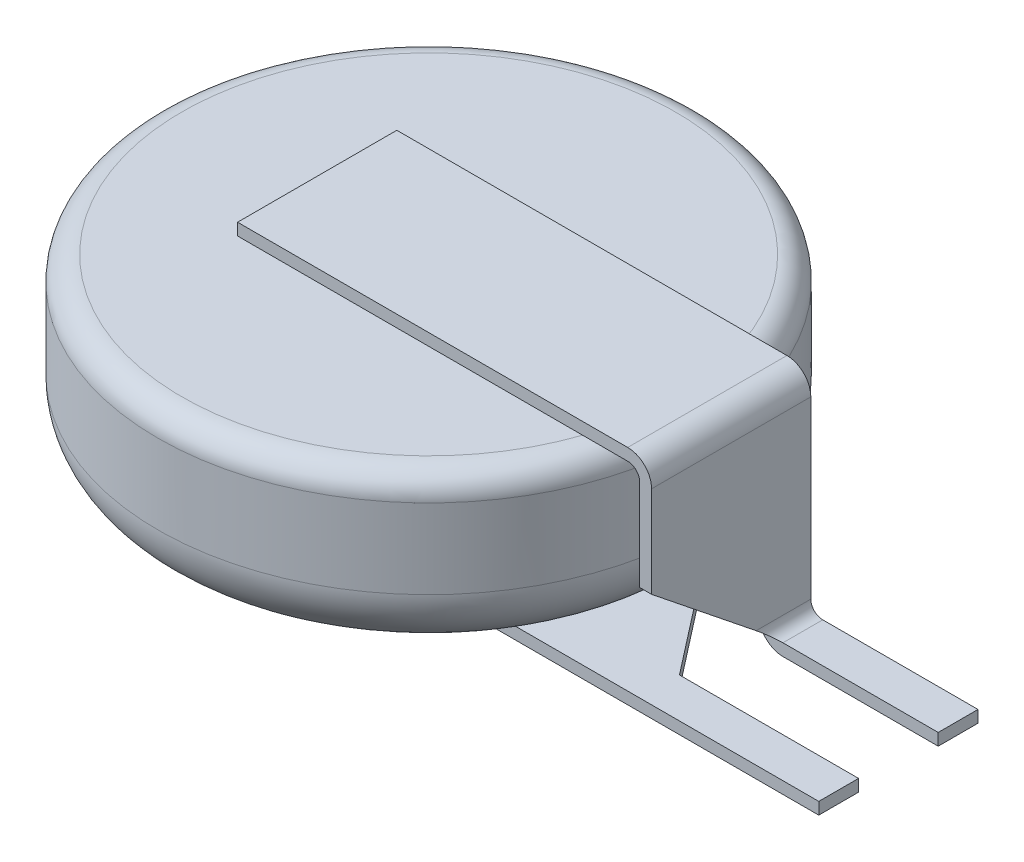
SolidWorks part; units mm, degrees
ref_plane "前视基准面" through (0, 0, 0) normal (0, 0, 1) x (1, 0, 0)
ref_plane "上视基准面" through (0, 0, 0) normal (0, 1, 0) x (1, 0, 0)
ref_plane "右视基准面" through (0, 0, 0) normal (1, 0, 0) x (0, 0, -1)
sketch "草图1" plane through (0, 0, 0) normal (0, 0, 1) x (1, 0, 0)
  line L0 (0, 0) -> (0, 2.8) construction
  line L1 (0.6006, 0.0061) -> (0.6006, 2.6398) construction
  line L2 (0, 2.65) -> (3.4, 2.65)
  line L3 (3.4, 2.65) -> (3.4, 0.552)
  line L4 (3.4, 0.552) -> (2.6, 0.552)
  line L5 (2.6, 0.552) -> (2.5054, 0.4126)
  line L6 (2.5054, 0.4126) -> (2.3701, 0.4126)
  line L7 (2.3701, 0.4126) -> (2.1919, 0.15)
  line L8 (2.1919, 0.15) -> (0, 0.15)
  line L9 (0, 2.65) -> (0, 0.15)
  line L10 (3.1725, 2.65) -> (3.4, 2.35) construction
  dimension "D1" = 2.8
  dimension "D2" = 3.4
  dimension "D3" = 2.5
  dimension "D4" = 0.15
  dimension "D5" = 0.8
  dimension "D6" = 124.16
  dimension "D7" = 0.3
revolve "旋转1" add sketch "草图1" angle 360 about L9
fillet "圆角1" radius 0.3 1 edges at (-3.4, 2.65, 0)
fillet "圆角2" radius 0.8 1 edges at (-3.4, 0.552, 0)
fillet "圆角3" radius 0.2 1 edges at (-2.1919, 0.15, 0)
sketch "草图3" plane through (0, 0, 0) normal (0, 0, 1) x (1, 0, 0)
  line L0 (-2.086, 0.15) -> (2.086, 0.15) construction
  line L1 (-1.7984, 0.15) -> (3.65, 0.15)
  line L2 (-1.7984, 0.15) -> (-1.7984, 0)
  line L3 (-1.7984, 0) -> (5.9, 0)
  line L4 (5.9, 0.15) -> (5.9, 0)
  line L5 (3.1, 2.65) -> (-3.1, 2.65) construction
  line L6 (-1.4, 2.65) -> (3.65, 2.65)
  line L7 (-1.4, 2.65) -> (-1.4, 2.8)
  line L8 (-1.4, 2.8) -> (3.8, 2.8)
  line L12 (3.8, 2.8) -> (3.8, 0.15)
  line L14 (3.65, 2.65) -> (3.65, 0.15)
  line L15 (3.8, 0.15) -> (5.9, 0.15)
  line L16 (3.4, 1.352) -> (3.4, 2.35) construction
  line L17 (3.65, 0.15) -> (3.8, 0.15) construction
  point P13 (-1.7984, 0.075)
  dimension "D1" = 2.5
  dimension "D2" = 2.1
  dimension "D3" = 1.4
  dimension "D4" = 1.8
extrude "凸台-拉伸1" add sketch "草图3" along normal mid plane 2
sketch "草图4" plane through (5.9, 0, 0) normal (1, 0, 0) x (0, 0, -1)
  line L0 (-1, 1.352) -> (0.5, 0.15)
  line L1 (-1, 0.15) -> (-1, 2.8) construction
  line L2 (-1, 0.15) -> (1, 0.15) construction
  line L3 (0.5, 0.15) -> (0.5, 0)
  line L4 (-1, 0) -> (1, 0) construction
  line L5 (0.5, 0) -> (-0.5, 0)
  line L6 (-0.5, 0) -> (-0.5, 0.15)
  line L7 (-0.5, 0.15) -> (-1, 0.15)
  line L8 (-1, 0.15) -> (-1, 1.352)
  line L9 (1, 0) -> (1, 0.15) construction
  line L10 (-1, 0) -> (-1, 0.15) construction
  line L11 (-3.4, 1.352) -> (3.4, 1.352) construction
  point P15 (1, 0.075)
  point P18 (-1, 0.075)
  point P19 (-1, 1.352)
  dimension "D1" = 0.5
  dimension "D2" = 0.5
extrude "切除-拉伸1" cut sketch "草图4" against normal up to surface (2.25 mm away) up to face at (3.65, 1.4, 0)
sketch "草图5" plane through (0, 0, 0) normal (0, -1, 0) x (1, 0, 0)
  line L0 (3.65, 0.5) -> (2.4845, -1)
  line L1 (-1.7984, -1) -> (5.9, -1) construction
  line L2 (2.4845, -1) -> (3.65, -1)
  line L3 (3.65, -1) -> (3.65, 0.5)
  point P7 (2.4845, -1)
extrude "切除-拉伸2" cut sketch "草图5" against normal blind 0.15
fillet "圆角5" radius 0.15 2 edges at (3.8, 0.15, -0.75) (3.65, 2.65, 0)
fillet "圆角4" radius 0.3 2 edges at (3.65, 0, -0.75) (3.8, 2.8, 0)
